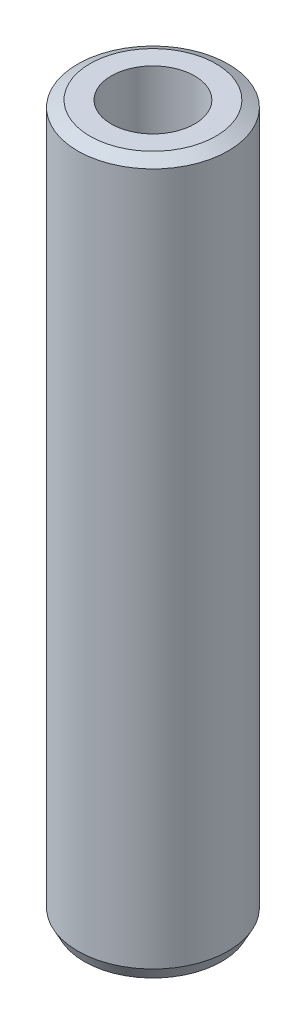
SolidWorks part; units mm, degrees
ref_plane "Front Plane" through (0, 0, 0) normal (0, 0, 1) x (1, 0, 0)
ref_plane "Top Plane" through (0, 0, 0) normal (0, 1, 0) x (1, 0, 0)
ref_plane "Right Plane" through (0, 0, 0) normal (1, 0, 0) x (0, 0, -1)
sketch "Sketch1" plane through (0, 0, 0) normal (0, 1, 0) x (1, 0, 0)
  circle A0 centre (0, 0) radius 57.5
  dimension "SHAFT_OD" = 115
extrude "Boss-Extrude1" add sketch "Sketch1" along normal blind 543.5859
sketch "Sketch2" plane through (0, 0, 0) normal (0, 1, 0) x (1, 0, 0)
  circle A0 centre (0, 0) radius 31.8417
  dimension "BORE_D" = 63.6834
extrude "Cut-Extrude1" cut sketch "Sketch2" along normal through all
chamfer "Chamfer1" distance 4.9868 angle 62.216 2 edges at (0, 543.5859, 57.5) (0, 0, 57.5) first distance on face at (0, 543.5859, 57.5) first distance on face at (0, 0, 31.8417)
